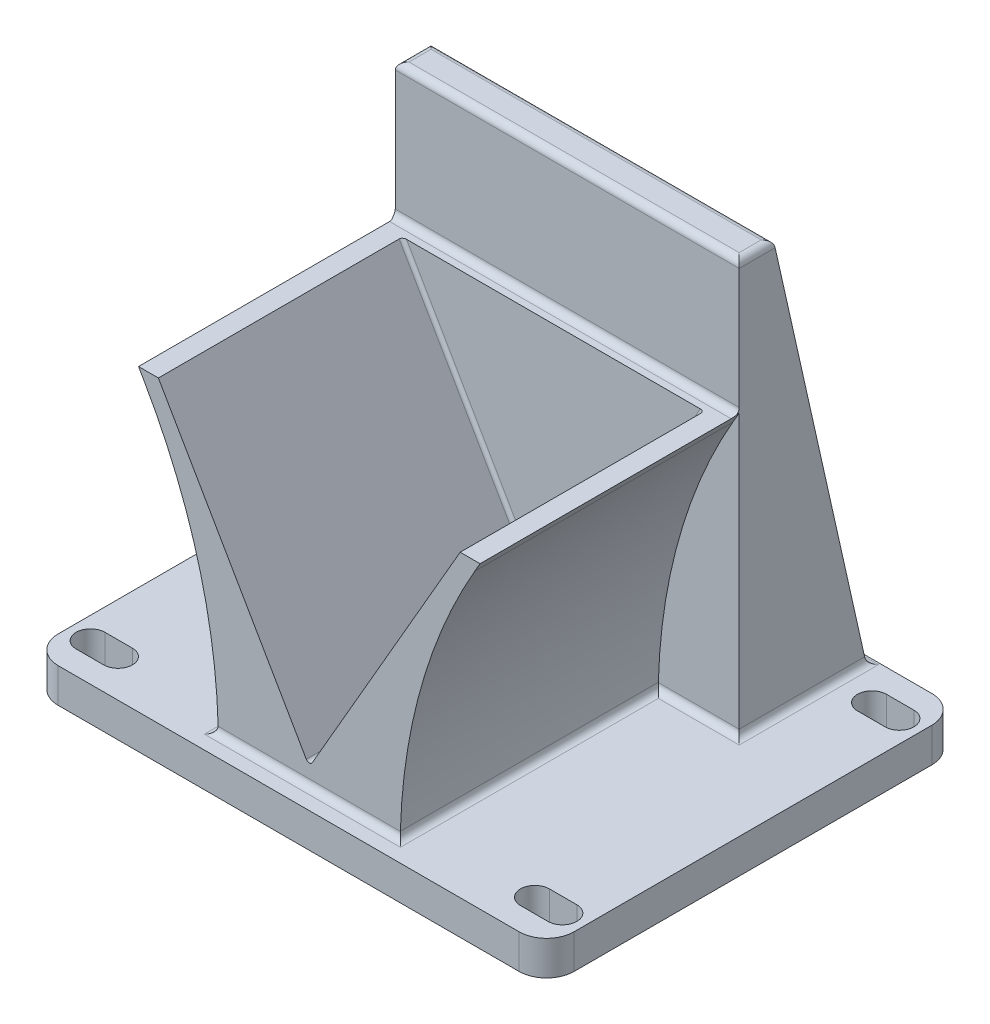
SolidWorks part; units mm, degrees
material "Cast Alloy Steel"
ref_plane "Front Plane" through (0, 0, 0) normal (0, 0, 1) x (1, 0, 0)
ref_plane "Top Plane" through (0, 0, 0) normal (0, 1, 0) x (1, 0, 0)
ref_plane "Right Plane" through (0, 0, 0) normal (1, 0, 0) x (0, 0, -1)
sketch "Sketch1" plane through (0, 0, 0) normal (0, 1, 0) x (1, 0, 0)
  line L1 (-33.5, -30) -> (33.5, -30)
  line L2 (-37.5, -26) -> (-37.5, 26)
  line L3 (-33.5, 30) -> (33.5, 30)
  line L4 (37.5, -26) -> (37.5, 26)
  line L5 (-37.5, -30) -> (37.5, 30) construction
  line L6 (-37.5, 30) -> (37.5, -30) construction
  arc A1 (33.5, -30) -> (37.5, -26) centre (33.5, -26) ccw
  arc A2 (33.5, 30) -> (37.5, 26) centre (33.5, 26) cw
  arc A3 (-37.5, 26) -> (-33.5, 30) centre (-33.5, 26) cw
  arc A4 (-33.5, -30) -> (-37.5, -26) centre (-33.5, -26) cw
  point P0 (0, 0)
  dimension "D2" = 60
  dimension "D3" = 4
  dimension "D4" = 4
  dimension "D1" = 75
extrude "Boss-Extrude1" add sketch "Sketch1" along normal blind 5
sketch "Sketch2" plane through (0, 5, 0) normal (0, 1, 0) x (1, 0, 0)
  line L0 (-36.7206, 0) -> (37.1077, 0) construction
  line L1 (0, 28.7379) -> (0, -20.7068) construction
  circle A0 centre (-29.3668, -23.8031) radius 2.5158
  circle A1 centre (29.3668, -23.8031) radius 2.5158
  circle A2 centre (29.3668, 23.8031) radius 2.5158
  circle A3 centre (-29.3668, 23.8031) radius 2.5158
extrude "Cut-Extrude1" [suppressed] cut sketch "Sketch2" against normal through all
ref_plane "Plane5" through (0, 0, 30) normal (0, 0, 1) x (1, 0, 0)
ref_plane "Plane6" through (0, 0, 27) normal (0, 0, 1) x (1, 0, 0)
sketch "Sketch11" plane through (0, 0, 27) normal (0, 0, 1) x (1, 0, 0)
  line L1 (0, 7.5) -> (21.9393, 45.5)
  line L2 (0, 9.3677) -> (0, 21.2728) construction
  line L5 (1.4434, 5) -> (24.8261, 45.5)
  line L6 (0, 7.5) -> (-21.9393, 45.5)
  line L7 (-33.5, 5) -> (33.5, 5) construction
  line L9 (-1.4434, 5) -> (-24.8261, 45.5)
  line L10 (-1.4434, 5) -> (1.4434, 5)
  line L11 (0, 2.5) -> (24.8261, 45.5) construction
  line L12 (0, 2.5) -> (-24.8261, 45.5) construction
  line L13 (-24.8261, 45.5) -> (-21.9393, 45.5)
  line L14 (0, 7.5) -> (-22.661, 46.75) construction
  line L15 (24.8261, 45.5) -> (21.9393, 45.5)
  line L16 (0, 7.5) -> (22.661, 46.75) construction
  dimension "D1" = 2.5
  dimension "D2" = 30
  dimension "D3" = 30
  dimension "D4" = 2.5
  dimension "D5" = 0
extrude "Boss-Extrude2" add sketch "Sketch11" against normal blind 37.5
sketch "Sketch13" plane through (0, 0, -10.5) normal (0, 0, -1) x (-1, 0, 0)
  line L0 (-24.8261, 45.5) -> (24.8261, 45.5)
  line L1 (24.8261, 45.5) -> (1.4434, 5)
  line L2 (1.4434, 5) -> (-1.4434, 5)
  line L3 (1.4434, 5) -> (-1.4434, 5) construction
  line L4 (-1.4434, 5) -> (-24.8261, 45.5)
extrude "Boss-Extrude4" add sketch "Sketch13" against normal blind 2
sketch "Sketch14" plane through (0, 5, 0) normal (0, 1, 0) x (1, 0, 0)
  line L0 (-25, 10.5) -> (25, 10.5)
  line L8 (-25, 10.5) -> (-25, 18)
  line L9 (-25, 18) -> (25, 18)
  line L10 (25, 10.5) -> (25, 18)
  line L11 (-25, 10.5) -> (25, 18) construction
  line L12 (-25, 18) -> (25, 10.5) construction
  line L13 (33.5, 30) -> (-33.5, 30) construction
  line L14 (-37.5, 26) -> (-37.5, -26) construction
  point P0 (0, 14.25)
  dimension "D1" = 37.5
  dimension "D2" = 12
  dimension "D6" = 50
  dimension "D7" = 7.5
extrude "Boss-Extrude5" [suppressed] add sketch "Sketch14" along normal blind 70
chamfer "Chamfer2" [suppressed] distance 2 angle 45
sketch "Sketch15" plane through (0, 5, 0) normal (0, 1, 0) x (1, 0, 0)
  line L0 (-34.3, -24.5) -> (-30.3, -24.5) construction
  line L1 (-34.3, -22.4) -> (-30.3, -22.4)
  line L2 (0, 28.273) -> (0, -17.8813) construction
  line L3 (-36.0717, 0) -> (36.8311, 0) construction
  line L4 (-34.3, -26.6) -> (-30.3, -26.6)
  line L5 (-33.5, -30) -> (33.5, -30) construction
  line L8 (34.3, -24.5) -> (30.3, -24.5) construction
  line L11 (34.3, -22.4) -> (30.3, -22.4)
  line L14 (-37.5, 26) -> (-37.5, -26) construction
  line L18 (34.3, -26.6) -> (30.3, -26.6)
  line L21 (-34.3, 24.5) -> (-30.3, 24.5) construction
  line L24 (-34.3, 22.4) -> (-30.3, 22.4)
  line L25 (-34.3, 26.6) -> (-30.3, 26.6)
  line L26 (34.3, 24.5) -> (30.3, 24.5) construction
  line L27 (34.3, 22.4) -> (30.3, 22.4)
  line L28 (34.3, 26.6) -> (30.3, 26.6)
  arc A3 (-34.3, -22.4) -> (-34.3, -26.6) centre (-34.3, -24.5) ccw
  arc A4 (-30.3, -26.6) -> (-30.3, -22.4) centre (-30.3, -24.5) ccw
  arc A17 (34.3, -22.4) -> (34.3, -26.6) centre (34.3, -24.5) cw
  arc A18 (30.3, -26.6) -> (30.3, -22.4) centre (30.3, -24.5) cw
  arc A19 (-34.3, 22.4) -> (-34.3, 26.6) centre (-34.3, 24.5) cw
  arc A20 (-30.3, 26.6) -> (-30.3, 22.4) centre (-30.3, 24.5) cw
  arc A21 (34.3, 22.4) -> (34.3, 26.6) centre (34.3, 24.5) ccw
  arc A22 (30.3, 26.6) -> (30.3, 22.4) centre (30.3, 24.5) ccw
  point P2 (-32.3, -24.5)
  point P16 (32.3, -24.5)
  point P23 (-32.3, 24.5)
  point P30 (32.3, 24.5)
  dimension "D3" = 3.2
  dimension "D4" = 5.5
  dimension "D1" = 4.2
  dimension "D2" = 4
extrude "Cut-Extrude2" cut sketch "Sketch15" against normal through all
ref_plane "Plane7" [suppressed] through (0, 0, 0) normal (1, 0, 0) x (0, 0, -1)
ref_plane "Plane8" through (0, 0, 0) normal (1, 0, 0) x (0, 0, -1)
sketch "Sketch19" plane through (0, 0, 0) normal (1, 0, 0) x (0, 0, -1)
  line L0 (10.5, 5) -> (10.5, 65)
  line L1 (28.9565, 5) -> (10.5, 5)
  line L2 (-22.4, 5) -> (-26.6, 5) construction
  line L3 (10.5, 65) -> (15.5, 65)
  line L4 (15.5, 65) -> (28.9565, 5)
  line L5 (10.5, 45.5) -> (10.5, 5) construction
  point P2 (28.9565, 5)
  point P3 (0, 0)
  dimension "D1" = 5
  dimension "D2" = 60
extrude "Boss-Extrude8" add sketch "Sketch19" along normal mid plane 50
ref_plane "Plane10" through (11.69, 0, 0) normal (1, 0, 0) x (0, 0, -1)
fillet "Fillet30" radius 0.5 1 edges at (0, 7.5, 9.25)
sketch "Sketch26" plane through (0, 0, -10.5) normal (0, 0, 1) x (1, 0, 0)
  line L0 (13.2217, 5) -> (1.4434, 5)
  line L1 (25, 5) -> (1.4434, 5) construction
  line L2 (1.4434, 5) -> (24.8261, 45.5) construction
  line L3 (13.2217, 5) -> (13.2217, 25.4006)
  line L4 (13.2217, 25.4006) -> (1.4434, 5)
  point P4 (13.2217, 5)
extrude "Boss-Extrude13" add sketch "Sketch26" along normal up to vertex (37.5 mm away) up to point (24.8261, 45.5, 27)
mirror "Mirror6" about plane through (0, 0, 0) normal (1, 0, 0) of "Boss-Extrude13"
fillet "Fillet32" radius 81 1 edges at (13.2217, 25.4006, 8.25)
fillet "Fillet33" radius 81 1 edges at (-13.2217, 25.4006, 8.25)
fillet "Fillet37" radius 1 1 edges at (0, 45.5, -10.5)
fillet "Fillet39" radius 1 1 edges at (0, 5, 27)
fillet "Fillet41" radius 1 2 edges at (19.1108, 5, -10.5) (13.2217, 5, 8.75)
fillet "Fillet42" radius 1 1 edges at (25, 5, -19.2283)
fillet "Fillet43" radius 1 1 edges at (0.5, 5, -28.9565)
fillet "Fillet44" radius 1 1 edges at (-25, 5, -20.1285)
fillet "Fillet45" radius 1 2 edges at (-13.2217, 5, 8.75) (-19.6108, 5, -10.5)
fillet "Fillet46" radius 1 4 edges at (0, 65, -15.5) (25, 65, -13) (0, 65, -10.5) (-25, 65, -13)
fillet "Fillet49" radius 0.5 3 edges at (-11.1862, 26.875, -8.5) (0, 8, -8.5) (11.1862, 26.875, -8.5)
